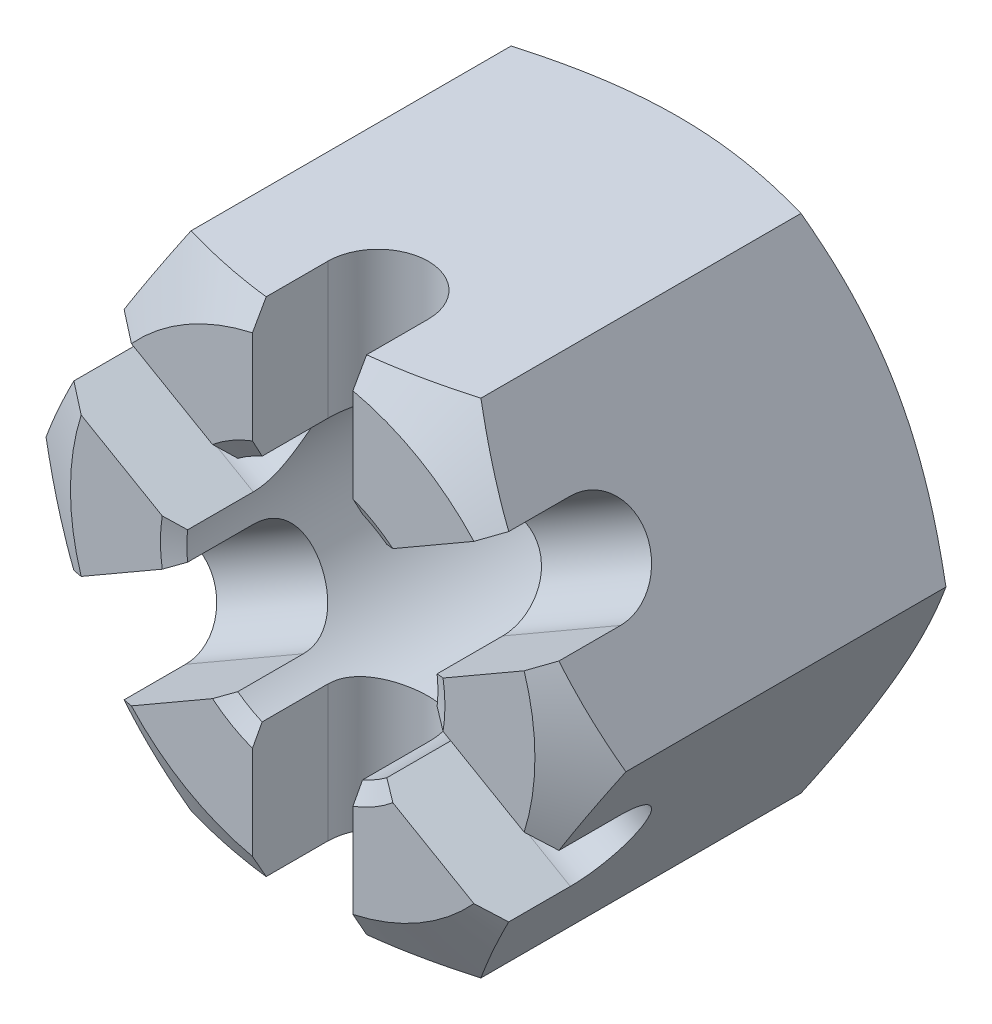
SolidWorks part; units mm, degrees
ref_plane "Front" through (0, 0, 0) normal (0, 0, 1) x (1, 0, 0)
ref_plane "Top" through (0, 0, 0) normal (0, 1, 0) x (1, 0, 0)
ref_plane "Right" through (0, 0, 0) normal (1, 0, 0) x (0, 0, -1)
sketch "Sketch1" plane through (0, 0, 0) normal (0, 0, 1) x (1, 0, 0)
  line L1 (2.8868, -5) -> (5.7735, 0)
  line L2 (5.7735, 0) -> (2.8868, 5)
  line L3 (2.8868, 5) -> (-2.8868, 5)
  line L4 (-2.8868, 5) -> (-5.7735, 0)
  line L5 (-5.7735, 0) -> (-2.8868, -5)
  line L6 (-2.8868, -5) -> (2.8868, -5)
  circle A0 centre (0, 0) radius 5 construction
  circle A1 centre (0, 0) radius 2.5
  dimension "D1" = 5
extrude "BaseNut" add sketch "Sketch1" against normal blind 7.7
cosmetic thread "ThreadCosmetic1" [suppressed] parameters "D"=6
sketch "Sketch2" plane through (0, 0, 0) normal (0, 1, 0) x (1, 0, 0)
  line L0 (-5.7735, 7.7) -> (-4.625, 7.7)
  line L2 (-4.625, 7.7) -> (-5.7735, 7.0369)
  line L3 (-5.7735, 7.0369) -> (-5.7735, 7.7)
  line L4 (0, 3.3759) -> (0, -9.8171) construction
  line L6 (-9.7712, 3.85) -> (9.8853, 3.85) construction
  line L7 (-5.7735, 0.6631) -> (-5.7735, 0)
  line L8 (-4.625, 0) -> (-5.7735, 0.6631)
  line L9 (-5.7735, 0) -> (-4.625, 0)
  line L10 (-5.7735, 7.7) -> (-5.7735, 0) construction
  dimension "D1" = 30
  dimension "D2" = 3.85
revolve "Double-Chamfer" cut sketch "Sketch2" angle 360 about L4
chamfer "EndChamfer" distance 0.3333 angle 30 2 edges at (2.5, 0, -7.7) (2.5, 0, 0) first distance on face at (2.5, 0, -7.7) first distance on face at (-4.625, 0, 0)
sketch "Sketch3" plane through (0, 0, 0) normal (0, 1, 0) x (1, 0, 0)
  line L0 (0, 4.2201) -> (0, -10.5237) construction
  line L2 (-1, 0) -> (-1, 1.5)
  line L3 (1, 0) -> (1, 1.5)
  line L4 (2.6925, 7.7) -> (-2.6925, 7.7) construction
  arc A0 (-1, 1.5) -> (1, 1.5) centre (0, 1.5) cw
  point P2 (0, 2.5)
  point P3 (0, 7.7)
  dimension "W" = 5.2
  dimension "D1" = 2.5
extrude "Slot" cut sketch "Sketch3" against normal through all and the other way through all
ref_axis "Axis1" through (0, 0, 1.7096) along (0, 0, -1)
pattern_circular "SlotPattern" count 3 over 360 about axis through (0, 0, 1.7096) along (0, 0, -1) of "Slot"
sketch "Sketch4" plane through (0, 0, 0) normal (0, 1, 0) x (1, 0, 0)
  line L0 (4.625, 0) -> (4.625, 2.5)
  line L2 (4.625, 2.5) -> (5.7735, 3.1631)
  line L4 (4.625, 0) -> (5.7735, 0)
  line L5 (5.7735, 0) -> (5.7735, 3.1631)
  line L7 (0, -0.375) -> (0, -8.8366) construction
  line L9 (4.4106, 0) -> (4.625, 0) construction
  line L10 (5.7735, 7.0369) -> (5.7735, 0.6631) construction
  dimension "D1" = 30
  dimension "W" = 5.2
revolve "Cut-Revolve1" [suppressed] cut sketch "Sketch4" angle 360 about L7
sketch "Sketch5" plane through (0, 0, 0) normal (0, 1, 0) x (1, 0, 0)
  line L0 (0, 9.8217) -> (0, -3.0923) construction
  line L1 (2, 7.6167) -> (2, 7.1167)
  line L2 (2, 7.1167) -> (2.5, 7.1167)
  line L3 (2.5, 7.1167) -> (2.933, 7.3667)
  line L4 (2.933, 7.3667) -> (2.5, 7.6167)
  line L5 (2.5, 7.6167) -> (2, 7.6167)
  line L6 (2.5, 7.3667) -> (-2.5, 7.3667) construction
  dimension "D1" = 0.5
  dimension "D2" = 5
revolve "Cut-Revolve10" [suppressed] cut sketch "Sketch5" angle 360 about L0
pattern_linear "LPattern10" [suppressed] count 12 spacing 0.6 along (0, 0, 1) of bodies 106
equation "\"dw@Sketch2\" = \"s@Sketch1\"-0.75"
equation "\"de@Sketch4\" = \"dw@Sketch2\""
equation "\"D1@Sketch3\" = \"m@BaseNut\" - \"W@Sketch3\""
equation "\"D2@Sketch2\" = \"m@BaseNut\" / 2"
equation "\"W@Sketch4\" = \"W@Sketch3\""
equation "\"D2@Sketch5\" = \"D1@Sketch1\""
equation "\"D1@Sketch5\" = (  \"D@ThreadCosmetic1\" - \"D1@Sketch1\" )  / 2"
equation "\"D3@LPattern10\" = \"D1@Sketch5\" * 1.2"
equation "\"D1@LPattern10\" = \"m@BaseNut\" / \"D3@LPattern10\" - 1"
equation "\"D1@EndChamfer\" = \"D1@Sketch1\" / 15"
